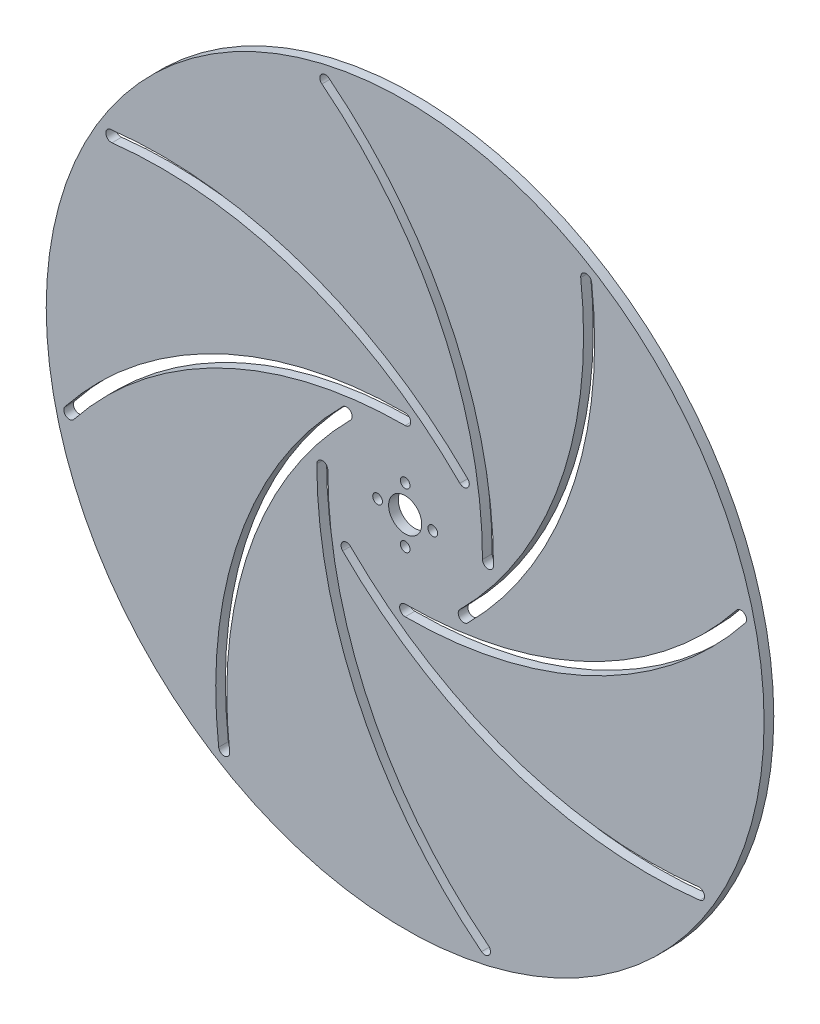
SolidWorks part; units mm, degrees
ref_plane "Front Plane" through (0, 0, 0) normal (0, 0, 1) x (1, 0, 0)
ref_plane "Top Plane" through (0, 0, 0) normal (0, 1, 0) x (1, 0, 0)
ref_plane "Right Plane" through (0, 0, 0) normal (1, 0, 0) x (0, 0, -1)
sketch "Sketch1" plane through (0, 0, 0) normal (0, 0, 1) x (1, 0, 0)
  line L0 (30, 0) -> (-130, 0) construction
  line L1 (0, 30) -> (0, -125) construction
  line L2 (0.5, 0) -> (0.5, 5.9791) construction
  line L3 (-0.5, 0) -> (-0.5, 5.9791) construction
  circle A0 centre (0, 0) radius 130
  circle A2 centre (0, 0) radius 30 construction
  circle A3 centre (0, 0) radius 125 construction
  arc A4 (0, 30) -> (-121.6133, -28.9) centre (0, -125) ccw construction
  arc A5 (0, 32) -> (-123.1825, -27.66) centre (0, -125) ccw
  arc A6 (0, 28) -> (-120.0441, -30.14) centre (0, -125) ccw
  arc A7 (0, 28) -> (0, 32) centre (0, 30) ccw
  arc A8 (-123.1825, -27.66) -> (-120.0441, -30.14) centre (-121.6133, -28.9) ccw
  arc A9 (21.2132, 21.2132) -> (-106.429, 65.5582) centre (-88.3883, -88.3883) ccw construction
  arc A14 (22.6274, 22.6274) -> (-106.6617, 67.5446) centre (-88.3883, -88.3883) ccw
  arc A19 (19.799, 19.799) -> (-106.1962, 63.5718) centre (-88.3883, -88.3883) ccw
  arc A24 (19.799, 19.799) -> (22.6274, 22.6274) centre (21.2132, 21.2132) ccw
  arc A29 (-106.6617, 67.5446) -> (-106.1962, 63.5718) centre (-106.429, 65.5582) ccw
  arc A35 (30, 0) -> (-28.9, 121.6133) centre (-125, 0) ccw construction
  arc A36 (32, 0) -> (-27.66, 123.1825) centre (-125, 0) ccw
  arc A37 (28, 0) -> (-30.14, 120.0441) centre (-125, 0) ccw
  arc A38 (28, 0) -> (32, 0) centre (30, 0) ccw
  arc A39 (-27.66, 123.1825) -> (-30.14, 120.0441) centre (-28.9, 121.6133) ccw
  arc A40 (21.2132, -21.2132) -> (65.5582, 106.429) centre (-88.3883, 88.3883) ccw construction
  arc A41 (22.6274, -22.6274) -> (67.5446, 106.6617) centre (-88.3883, 88.3883) ccw
  arc A42 (19.799, -19.799) -> (63.5718, 106.1962) centre (-88.3883, 88.3883) ccw
  arc A43 (19.799, -19.799) -> (22.6274, -22.6274) centre (21.2132, -21.2132) ccw
  arc A44 (67.5446, 106.6617) -> (63.5718, 106.1962) centre (65.5582, 106.429) ccw
  arc A45 (0, -30) -> (121.6133, 28.9) centre (0, 125) ccw construction
  arc A46 (0, -32) -> (123.1825, 27.66) centre (0, 125) ccw
  arc A47 (0, -28) -> (120.0441, 30.14) centre (0, 125) ccw
  arc A48 (0, -28) -> (0, -32) centre (0, -30) ccw
  arc A49 (123.1825, 27.66) -> (120.0441, 30.14) centre (121.6133, 28.9) ccw
  arc A50 (-21.2132, -21.2132) -> (106.429, -65.5582) centre (88.3883, 88.3883) ccw construction
  arc A51 (-22.6274, -22.6274) -> (106.6617, -67.5446) centre (88.3883, 88.3883) ccw
  arc A52 (-19.799, -19.799) -> (106.1962, -63.5718) centre (88.3883, 88.3883) ccw
  arc A53 (-19.799, -19.799) -> (-22.6274, -22.6274) centre (-21.2132, -21.2132) ccw
  arc A54 (106.6617, -67.5446) -> (106.1962, -63.5718) centre (106.429, -65.5582) ccw
  arc A55 (-30, 0) -> (28.9, -121.6133) centre (125, 0) ccw construction
  arc A56 (-32, 0) -> (27.66, -123.1825) centre (125, 0) ccw
  arc A57 (-28, 0) -> (30.14, -120.0441) centre (125, 0) ccw
  arc A58 (-28, 0) -> (-32, 0) centre (-30, 0) ccw
  arc A59 (27.66, -123.1825) -> (30.14, -120.0441) centre (28.9, -121.6133) ccw
  arc A60 (-21.2132, 21.2132) -> (-65.5582, -106.429) centre (88.3883, -88.3883) ccw construction
  arc A61 (-22.6274, 22.6274) -> (-67.5446, -106.6617) centre (88.3883, -88.3883) ccw
  arc A62 (-19.799, 19.799) -> (-63.5718, -106.1962) centre (88.3883, -88.3883) ccw
  arc A63 (-19.799, 19.799) -> (-22.6274, 22.6274) centre (-21.2132, 21.2132) ccw
  arc A64 (-67.5446, -106.6617) -> (-63.5718, -106.1962) centre (-65.5582, -106.429) ccw
  circle A65 centre (0, 0) radius 6
  arc A66 (-0.5, 3.4641) -> (0.5, 3.4641) centre (0, 0) cw
  arc A67 (-0.5, 5.9791) -> (0.6667, 5.9628) centre (0, 0) cw
  circle A68 centre (0, 0) radius 10 construction
  circle A69 centre (0, -10) radius 1.75
  circle A70 centre (-10, 0) radius 1.75
  circle A71 centre (0, 10) radius 1.75
  circle A72 centre (10, 0) radius 1.75
  point P11 (-67.5629, 14.5)
  point P22 (-37.5212, 58.0273)
  point P30 (14.5, 67.5629)
  point P38 (58.0273, 37.5212)
  point P46 (67.5629, -14.5)
  point P54 (37.5212, -58.0273)
  point P59 (-0.3062, 0.1031)
  point P63 (-14.5, -67.5629)
  point P71 (-58.0273, -37.5212)
  point P76 (0, 0)
  point P93 (0, 0)
  dimension "D2" = 260
  dimension "D3" = 250
  dimension "D4" = 60
  dimension "D5" = 4
  dimension "D6" = 4
  dimension "D8" = 12
  dimension "D9" = 0.5
  dimension "D10" = 0.5
  dimension "D7" = 8
extrude "Boss-Extrude1" add sketch "Sketch1" along normal blind 1.75 and the other way blind 1.75 contours A0 A54 A51 A53 A52 A49 A46 A48 A47 A8 A5 A7 A6 | A65 region at (-126.323, 0, 0)
